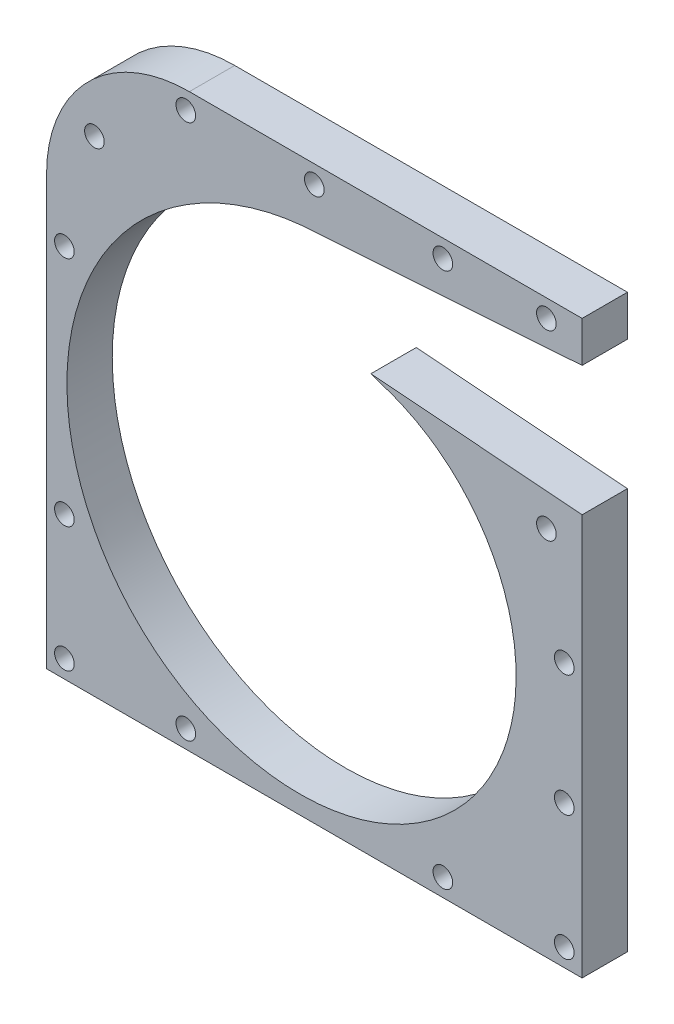
SolidWorks part; units mm, degrees
material "AISI 304"
ref_plane "Front Plane" through (0, 0, 0) normal (0, 0, 1) x (1, 0, 0)
ref_plane "Top Plane" through (0, 0, 0) normal (0, 1, 0) x (1, 0, 0)
ref_plane "Right Plane" through (0, 0, 0) normal (1, 0, 0) x (0, 0, -1)
sketch "Sketch1" plane through (0, 0, 0) normal (0, 0, 1) x (1, 0, 0)
  line L1 (-18.1818, -7.7823) -> (131.8182, -7.7823)
  line L2 (-18.1818, -7.7823) -> (-18.1818, 152.2177)
  line L3 (-18.1818, 152.2177) -> (131.8182, 152.2177)
  line L4 (131.8182, -7.7823) -> (131.8182, 152.2177)
  dimension "D1" = 160
  dimension "D2" = 150
extrude "Boss-Extrude1" add sketch "Sketch1" along normal blind 12.7
sketch "Sketch2" plane through (0, 0, 0) normal (0, 0, 1) x (1, 0, 0)
  line L0 (-18.1818, -7.7823) -> (131.8182, -7.7823) construction
  line L1 (56.8182, -7.7823) -> (56.8182, 152.2177) construction
  line L2 (131.8182, 152.2177) -> (-18.1818, 152.2177) construction
  line L3 (-18.1818, -7.7823) -> (131.8182, -7.7823) construction
  circle A0 centre (56.8182, 60.2177) radius 50.8 construction
  circle A1 centre (56.8182, 60.2177) radius 51.5
  point P0 (56.8182, 52.2686)
  dimension "D2" = 101.6
  dimension "D3" = 103
  dimension "D1" = 60.0509
  dimension "D4" = 68
extrude "Cut-Extrude2" cut sketch "Sketch2" along normal up to next
sketch "Sketch3" plane through (0, 0, 0) normal (0, 0, -1) x (-1, 0, 0)
  line L0 (-42.4775, -245.3976) -> (306.8559, -245.3976) construction
  line L1 (-107.6182, 60.2177) -> (-6.0182, 60.2177) construction
  line L3 (-130.5969, 104.5788) -> (-130.5969, 140.8094)
  line L4 (-130.5969, 104.5788) -> (-77.2525, 107.4902)
  circle A0 centre (-56.8182, 60.2177) radius 50.8 construction
  circle A1 centre (-56.8182, 60.2177) radius 51.5 construction
  circle A2 centre (-56.8182, 60.2177) radius 51.5
  point P5 (-77.2525, 107.4902)
  point P6 (-120.0714, 60.0509)
  point P9 (-63.5, -2.7792)
  point P10 (20.4545, 64.0852)
  point P13 (5.2437, 60.0509)
  point P14 (-63.5, 134.174)
  point P15 (-130.5969, 140.8094)
  point P16 (-130.5969, 104.5788)
  dimension "D1" = 101.6
sketch "Sketch5" plane through (0, 0, 0) normal (0, 0, 1) x (1, 0, 0)
  circle A0 centre (56.8182, 60.2177) radius 51.1201
curve "Helix/Spiral2"
sketch "Sketch8" plane through (0, 0, 12.7) normal (0, 0, 1) x (1, 0, 0)
  line L0 (58.9317, 135.8843) -> (131.8182, 140.8094)
  line L1 (131.8182, 140.8094) -> (131.8182, 104.5788)
  line L2 (131.8182, 104.5788) -> (70.9088, 109.3575)
  line L3 (131.8182, -7.7823) -> (131.8182, 152.2177) construction
  spline S0 degree 3 poles (1651.8411, -1079.5367) (-229.7192, -143.5522) (-21.1382, 148.1207) (83.2388, 105.2908) (86.1686, 103.7524) (91.7235, 100.1208) (94.3486, 98.0276) (99.1887, 93.3472) (101.4036, 90.76) (105.3304, 85.1727) (107.0421, 82.1726) (109.8854, 75.8577) (111.0169, 72.5431) (112.6419, 65.712) (113.1355, 62.1958) (113.449, 55.0847) (113.269, 51.4901) (112.2238, 44.352) (111.3586, 40.8087) (108.9564, 33.9042) (107.4194, 30.5432) (103.7119, 24.1311) (101.5416, 21.0801) (96.6303, 15.4078) (93.8895, 12.7866) (87.9227, 8.0805) (84.6968, 5.9958) (77.8655, 2.4525) (74.2601, 0.9941) (66.7916, -1.2278) (62.9287, -1.991) (55.0798, -2.7774) (51.0939, -2.8005) (43.1413, -2.0875) (39.1747, -1.3513) (31.4057, 0.8716) (27.6034, 2.3584) (20.3052, 6.0466) (16.8095, 8.248) (10.2591, 13.3019) (7.2045, 16.1545) (1.6578, 22.4224) (-0.8343, 25.8377) (-5.1525, 33.1198) (-6.9784, 36.9865) (-9.8828, 45.0414) (-10.9611, 49.2293) (-12.3142, 57.7818) (-12.5888, 62.1461) (-12.3065, 70.8967) (-11.7496, 75.2828) (-9.8061, 83.9183) (-8.4194, 88.1675) (-4.8487, 96.372) (-2.6646, 100.3271) (2.4392, 107.7936) (5.3588, 111.3049) (11.8435, 117.7469) (15.4084, 120.6775) (23.0682, 125.8397) (27.1629, 128.0712) (35.745, 131.7396) (40.2322, 133.1765) (177.9482, 163.235) (410.4015, -168.0858) (-1258.2145, -1322.1018) knots -1.015613 -1.015613 -1.015613 -1.015613 0.03125 0.03125 0.0625 0.0625 0.09375 0.09375 0.125 0.125 0.15625 0.15625 0.1875 0.1875 0.21875 0.21875 0.25 0.25 0.28125 0.28125 0.3125 0.3125 0.34375 0.34375 0.375 0.375 0.40625 0.40625 0.4375 0.4375 0.46875 0.46875 0.5 0.5 0.53125 0.53125 0.5625 0.5625 0.59375 0.59375 0.625 0.625 0.65625 0.65625 0.6875 0.6875 0.71875 0.71875 0.75 0.75 0.78125 0.78125 0.8125 0.8125 0.84375 0.84375 0.875 0.875 0.90625 0.90625 0.9375 0.9375 0.96875 0.96875 1.871775 1.871775 1.871775 1.871775 only from (70.9088, 109.3575) to (58.9317, 135.8843) construction
  spline S1 degree 3 poles (70.9088, 109.3575) (74.0669, 108.7182) (77.1879, 107.7737) (83.2388, 105.2908) (86.1686, 103.7524) (91.7235, 100.1208) (94.3486, 98.0276) (99.1887, 93.3472) (101.4036, 90.76) (105.3304, 85.1727) (107.0421, 82.1726) (109.8854, 75.8577) (111.0169, 72.5431) (112.6419, 65.712) (113.1355, 62.1958) (113.449, 55.0847) (113.269, 51.4901) (112.2238, 44.352) (111.3586, 40.8087) (108.9564, 33.9042) (107.4194, 30.5432) (103.7119, 24.1311) (101.5416, 21.0801) (96.6303, 15.4078) (93.8895, 12.7866) (87.9227, 8.0805) (84.6968, 5.9958) (77.8655, 2.4525) (74.2601, 0.9941) (66.7916, -1.2278) (62.9287, -1.991) (55.0798, -2.7774) (51.0939, -2.8005) (43.1413, -2.0875) (39.1747, -1.3513) (31.4057, 0.8716) (27.6034, 2.3584) (20.3052, 6.0466) (16.8095, 8.248) (10.2591, 13.3019) (7.2045, 16.1545) (1.6578, 22.4224) (-0.8343, 25.8377) (-5.1525, 33.1198) (-6.9784, 36.9865) (-9.8828, 45.0414) (-10.9611, 49.2293) (-12.3142, 57.7818) (-12.5888, 62.1461) (-12.3065, 70.8967) (-11.7496, 75.2828) (-9.8061, 83.9183) (-8.4194, 88.1675) (-4.8487, 96.372) (-2.6646, 100.3271) (2.4392, 107.7936) (5.3588, 111.3049) (11.8435, 117.7469) (15.4084, 120.6775) (23.0682, 125.8397) (27.1629, 128.0712) (35.745, 131.7396) (40.2322, 133.1765) (49.445, 135.1873) (54.1703, 135.7612) (58.9317, 135.8843) knots 0 0 0 0 0.03125 0.03125 0.0625 0.0625 0.09375 0.09375 0.125 0.125 0.15625 0.15625 0.1875 0.1875 0.21875 0.21875 0.25 0.25 0.28125 0.28125 0.3125 0.3125 0.34375 0.34375 0.375 0.375 0.40625 0.40625 0.4375 0.4375 0.46875 0.46875 0.5 0.5 0.53125 0.53125 0.5625 0.5625 0.59375 0.59375 0.625 0.625 0.65625 0.65625 0.6875 0.6875 0.71875 0.71875 0.75 0.75 0.78125 0.78125 0.8125 0.8125 0.84375 0.84375 0.875 0.875 0.90625 0.90625 0.9375 0.9375 0.96875 0.96875 1 1 1 1
extrude "Cut-Extrude3" cut sketch "Sketch8" against normal up to next
fillet "Fillet1" radius 40 1 edges at (-18.1818, 152.2177, 6.35)
sketch "Sketch9" plane through (0, 0, 12.7) normal (0, 0, 1) x (1, 0, 0)
  line L0 (131.8182, 140.8094) -> (131.8182, 152.2177) construction
  line L1 (126.8182, 152.2177) -> (126.8182, -7.7823) construction
  line L2 (131.8182, 152.2177) -> (21.8182, 152.2177) construction
  line L3 (-18.1818, -7.7823) -> (131.8182, -7.7823) construction
  line L4 (131.8182, -7.7823) -> (131.8182, 104.5788) construction
  circle A1 centre (121.8182, 147.2177) radius 2.75
  circle A3 centre (92.8182, 147.2177) radius 2.75
  circle A5 centre (56.8182, 147.2177) radius 2.75
  circle A6 centre (20.8182, 147.2177) radius 2.75
  circle A7 centre (-4.7746, 128.0936) radius 2.75
  circle A8 centre (-13.1818, 97.2177) radius 2.75
  circle A9 centre (-13.1818, 32.2177) radius 2.75
  circle A10 centre (-13.1818, -2.7823) radius 2.75
  circle A11 centre (20.8182, -2.7823) radius 2.75
  circle A12 centre (92.8182, -2.7823) radius 2.75
  circle A13 centre (126.8182, -2.7823) radius 2.75
  circle A14 centre (126.8182, 32.2177) radius 2.75
  circle A15 centre (126.8182, 66.2177) radius 2.75
  circle A16 centre (121.8182, 96.2177) radius 2.75
  dimension "D11" = 10
  dimension "D2" = 29
  dimension "D3" = 36
  dimension "D4" = 31.9488
  dimension "D5" = 32
  dimension "D6" = 35
  dimension "D7" = 34
  dimension "D8" = 34
  dimension "D9" = 35
  dimension "D10" = 34
  dimension "D12" = 36
  dimension "D13" = 5
  dimension "D14" = 30
  dimension "D15" = 10
extrude "Cut-Extrude4" cut sketch "Sketch9" against normal up to next
